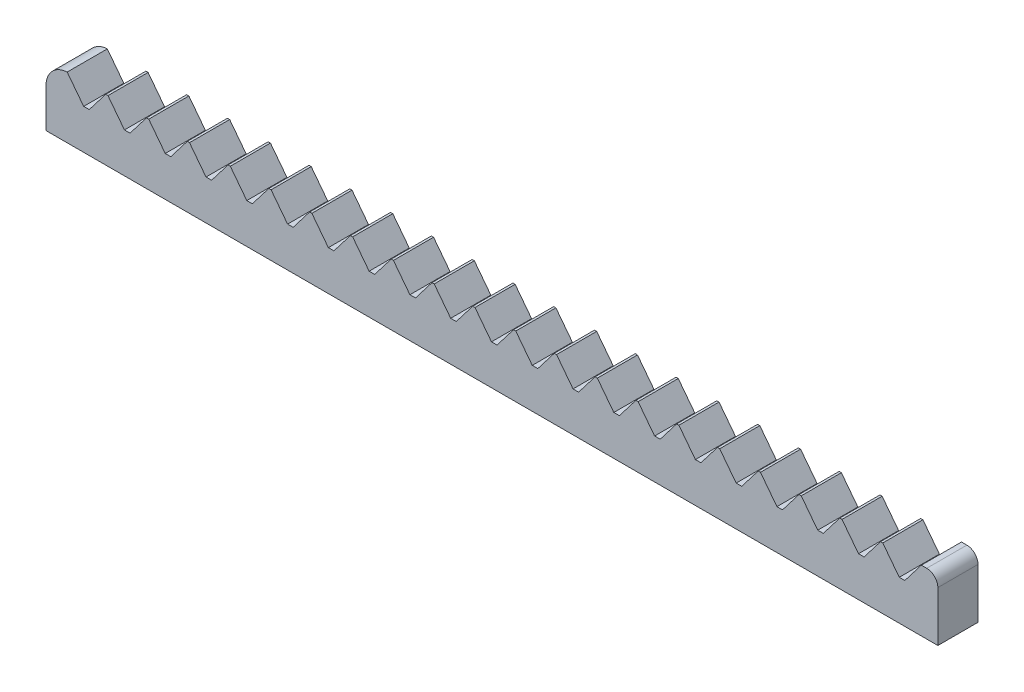
SolidWorks part; units mm, degrees
ref_plane "Ebene vorne" through (0, 0, 0) normal (0, 0, 1) x (1, 0, 0)
ref_plane "Ebene oben" through (0, 0, 0) normal (0, 1, 0) x (1, 0, 0)
ref_plane "Ebene rechts" through (0, 0, 0) normal (1, 0, 0) x (0, 0, -1)
sketch "Skizze1" plane through (0, 0, 0) normal (0, 0, 1) x (1, 0, 0)
  line L0 (-38.7467, 0) -> (43.3913, 0) construction
  line L2 (-30.8846, 5.5) -> (49.1154, 5.5)
  line L3 (-30.8846, 5.5) -> (-30.8846, 0)
  line L4 (-30.8846, 0) -> (49.1154, 0)
  line L5 (49.1154, 5.5) -> (49.1154, 0)
  dimension "D1" = 5.5
  dimension "D2" = 80
extrude "Koerper" add sketch "Skizze1" along normal mid plane 3.6
sketch "kerbe" plane through (0, 0, 1.8) normal (0, 0, 1) x (1, 0, 0)
  line L0 (-30.8846, 3.5712) -> (49.1154, 3.5712) construction
  line L1 (-30.8846, 5.5) -> (-30.8846, 0) construction
  line L2 (49.1154, 0) -> (49.1154, 5.5) construction
  line L3 (-29.0846, 5.5) -> (-28.9846, 5.5)
  line L4 (49.1154, 5.5) -> (-30.8846, 5.5) construction
  line L5 (-28.9846, 5.5) -> (-27.5056, 3.5712)
  line L6 (-27.5056, 3.5712) -> (-27.0056, 3.5712)
  line L7 (-27.0056, 3.5712) -> (-25.5266, 5.5)
  line L8 (-25.5266, 5.5) -> (-25.4266, 5.5)
  dimension "D1" = 1.8
  dimension "D2" = 0.5
  dimension "D3" = 0.1
  dimension "D4" = 3.658
extrude "Schnitt-Linear austragen1" cut sketch "kerbe" against normal through all and the other way through all
pattern_linear "Lineares Muster10" count 21 spacing 3.658 along (1, 0, 0) of "Schnitt-Linear austragen1"
fillet "Verrundung1" radius 2 1 edges at (-30.8846, 5.5, 0)
fillet "Verrundung2" radius 1 1 edges at (49.1154, 5.5, 0)
